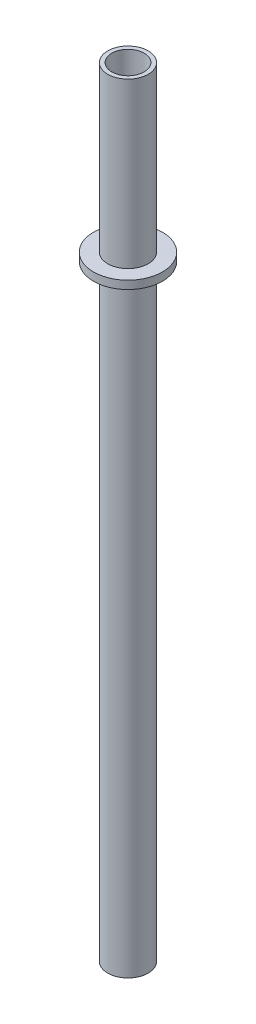
SolidWorks part; units mm, degrees
material "Plain Carbon Steel"
ref_plane "Front Plane" through (0, 0, 0) normal (0, 0, 1) x (1, 0, 0)
ref_plane "Top Plane" through (0, 0, 0) normal (0, 1, 0) x (1, 0, 0)
ref_plane "Right Plane" through (0, 0, 0) normal (1, 0, 0) x (0, 0, -1)
sketch "Sketch1" plane through (0, 0, 0) normal (0, 1, 0) x (1, 0, 0)
  circle A0 centre (0, 0) radius 15.875
  circle A1 centre (0, 0) radius 12.7
  dimension "D1" = 31.75
  dimension "D2" = 25.4
extrude "Shaft extrusion" add sketch "Sketch1" along normal blind 134.8684 and the other way blind 474.7316
sketch "Sketch2" plane through (0, 0, 0) normal (0, 1, 0) x (1, 0, 0)
  circle A0 centre (0, 0) radius 26.9875
  circle A1 centre (0, 0) radius 15.875 construction
  circle A2 centre (0, 0) radius 15.875
  dimension "D1" = 53.975
extrude "Boss-Extrude1" add sketch "Sketch2" along normal blind 6.35
